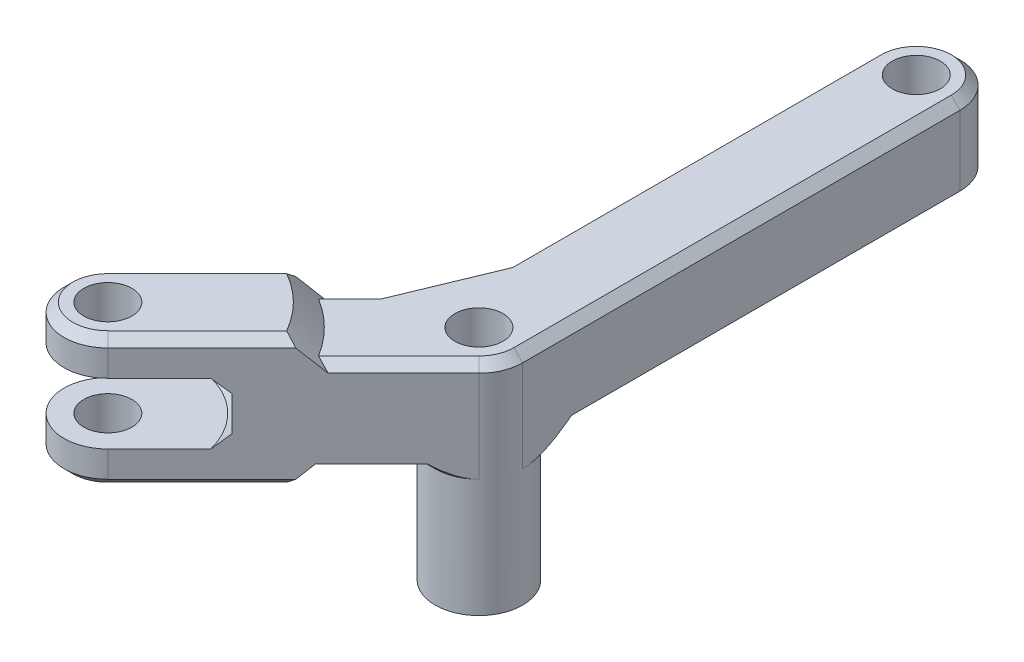
SolidWorks part; units mm, degrees
ref_plane "前视基准面" through (0, 0, 0) normal (0, 0, 1) x (1, 0, 0)
ref_plane "上视基准面" through (0, 0, 0) normal (0, 1, 0) x (1, 0, 0)
ref_plane "右视基准面" through (0, 0, 0) normal (1, 0, 0) x (0, 0, -1)
other "Configuration Table"
sketch "草图1" plane through (0, 0, 0) normal (0, 1, 0) x (1, 0, 0)
  line L0 (0, 0) -> (0, 50) construction
  line L1 (0, 0) -> (-21.2132, -21.2132) construction
  line L2 (-5, 2.0711) -> (-5, 50)
  line L3 (-17.6777, -24.7487) -> (3.5355, -3.5355)
  line L4 (-24.7487, -17.6777) -> (-5, 2.0711)
  line L5 (5, 0) -> (5, 50)
  arc A1 (-24.7487, -17.6777) -> (-17.6777, -24.7487) centre (-21.2132, -21.2132) ccw
  arc A2 (5, 50) -> (-5, 50) centre (0, 50) ccw
  arc A3 (3.5355, -3.5355) -> (5, 0) centre (0, 0) ccw
  dimension "D1" = 5
  dimension "D3" = 10
  dimension "D6" = 10
  dimension "D8" = 225
  dimension "D2" = 135
  dimension "D4" = 30
  dimension "D5" = 50
  dimension "D7" = 10
  dimension "D9" = 135
extrude "凸台-拉伸1" add sketch "草图1" along normal blind 10
sketch "草图3" plane through (0, 0, 0) normal (0, 1, 0) x (1, 0, 0)
  circle A0 centre (0, 0) radius 5
extrude "凸台-拉伸2" add sketch "草图3" against normal blind 15
sketch "草图4" plane through (0, 0, 0) normal (0, 1, 0) x (1, 0, 0)
  circle A0 centre (0, 0) radius 2.75
  dimension "D1" = 5.5
extrude "切除-拉伸1" cut sketch "草图4" against normal up to surface (15 mm away) from surface up to face at (0, -15, 5) starting at face at (-6.0107, 10, -8.204)
sketch "草图5" plane through (0, 0, 0) normal (0, 1, 0) x (1, 0, 0)
  circle A0 centre (-21.2132, -21.2132) radius 2.75
  dimension "D1" = 5.5
extrude "切除-拉伸2" cut sketch "草图5" against normal up to surface from surface up to face at (-7.3305, 0, -8.7507) starting at face at (0, 10, 2.75)
sketch "草图6" plane through (0, 0, 0) normal (0, 1, 0) x (1, 0, 0)
  circle A0 centre (-21.2132, -21.2132) radius 11.2
  dimension "D1" = 22.4
extrude "切除-拉伸3" cut sketch "草图6" along normal blind 7 from offset 1.5
sketch "草图7" plane through (0, 0, 0) normal (0, 1, 0) x (1, 0, 0)
  line L0 (-17.6777, -24.7487) -> (3.5355, -3.5355) construction
  line L1 (-5, 2.0711) -> (-24.7487, -17.6777) construction
  line L2 (-17.6777, -24.7487) -> (-7.6777, -14.7487)
  line L3 (-14.7487, -7.6777) -> (-24.7487, -17.6777)
  arc A0 (-7.6777, -14.7487) -> (-14.7487, -7.6777) centre (-21.2132, -21.2132) ccw
  arc A1 (-24.7487, -17.6777) -> (-17.6777, -24.7487) centre (-21.2132, -21.2132) ccw construction
  arc A2 (-24.7487, -17.6777) -> (-17.6777, -24.7487) centre (-21.2132, -21.2132) ccw
  dimension "D1" = 30
extrude "凸台-拉伸3" add sketch "草图7" along normal blind 2.5 from surface starting at face at (-21.2132, 10, 23.9632)
extrude "凸台-拉伸4" add sketch "草图7<2>" against normal blind 2.5
sketch "草图7<2>" plane through (0, 0, 0) normal (0, 1, 0) x (1, 0, 0) same geometry as "草图7"
chamfer "倒角1" distance 2.5 angle 45 2 edges at (-10.6066, 0, 10.6066) (-10.6066, 10, 10.6066)
sketch "草图8" plane through (0, 0, 0) normal (0, 1, 0) x (1, 0, 0)
  circle A0 centre (-21.2132, -21.2132) radius 2.75
  dimension "D1" = 5.5
extrude "切除-拉伸4" cut sketch "草图8" along normal up to surface (12.5 mm away) from surface up to face at (-16.9454, 12.5, 16.9454) starting at face at (-16.9454, -2.5, 16.9454)
sketch "草图9" plane through (0, 0, 0) normal (0, 1, 0) x (1, 0, 0)
  circle A0 centre (0, 50) radius 2.75
  dimension "D1" = 5.5
extrude "切除-拉伸5" cut sketch "草图9" against normal up to surface from surface up to face at (-3.3636, 0, -12.7176) starting at face at (-2.0438, 10, -12.1709)
sketch "草图10" plane through (0, 0, 0) normal (0, 1, 0) x (1, 0, 0)
  line L0 (-5, 8.0711) -> (-9.2426, -2.1716)
  line L1 (-5, 50) -> (-5, 2.0711) construction
  line L2 (-5, 2.0711) -> (-12.8902, -5.8191) construction
  line L3 (-9.2426, -2.1716) -> (-5, 2.0711)
  line L4 (-5, 2.0711) -> (-5, 8.0711)
  dimension "D1" = 6
  dimension "D2" = 6
extrude "凸台-拉伸5" add sketch "草图10" against normal up to surface from surface up to face at (0, 0, -47.25) starting at face at (0, 10, -47.25)
chamfer "倒角2" distance 1.5 angle 45 3 edges at (-13.2936, 8.5, 13.2936) (-13.2936, 1.5, 13.2936) (-4.6194, 0, -1.9134)
chamfer "倒角3" distance 1 angle 45 18 edges at (4.6194, 10, 1.9134) (-1.1418, 10, 8.2129) (5, 10, -25) (0, 10, -55) (-5, 10, -29.0355) (-7.1213, 10, -2.9497) (-11.0664, 10, 3.9954) (5, 0, -27.0767) (0, 0, -55) (-5, 0, -29.0355) (-7.1213, 0, -2.9497) (-11.0664, 0, 3.9954) (-19.7487, -2.5, 12.6777) (-24.7487, -2.5, 24.7487) (-12.6777, -2.5, 19.7487) (-19.7487, 12.5, 12.6777) (-24.7487, 12.5, 24.7487) (-12.6777, 12.5, 19.7487)
